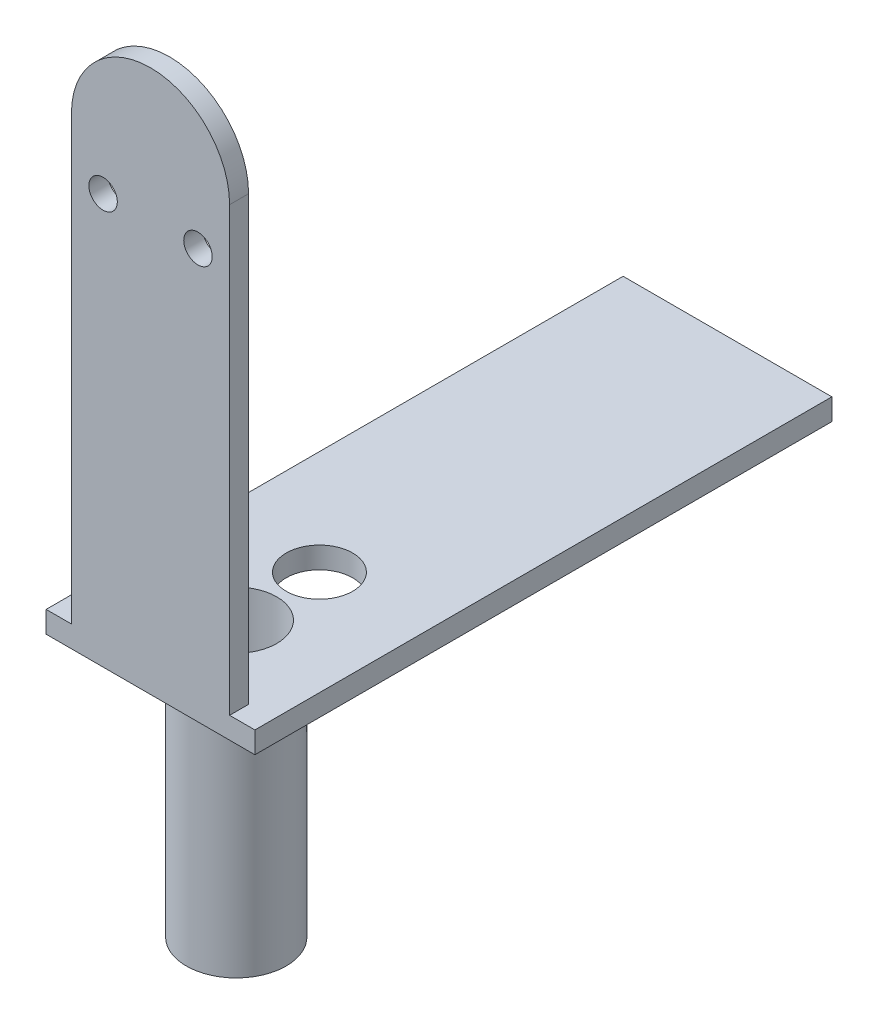
SolidWorks part; units mm, degrees
ref_plane "Front Plane" through (0, 0, 0) normal (0, 0, 1) x (1, 0, 0)
ref_plane "Top Plane" through (0, 0, 0) normal (0, 1, 0) x (1, 0, 0)
ref_plane "Right Plane" through (0, 0, 0) normal (1, 0, 0) x (0, 0, -1)
sketch "Sketch1" plane through (0, 0, 0) normal (0, 0, 1) x (1, 0, 0)
  line L0 (0, 0) -> (33, 0)
  line L1 (16.5, 0) -> (29, 0)
  line L2 (16.5, 0) -> (16.5, 9.4766)
  line L3 (4, 0) -> (4, 80.5)
  line L4 (29, 0) -> (29, 80.5)
  line L5 (0, 0) -> (0, 80.5)
  line L6 (0, 80.5) -> (4, 80.5)
  line L7 (33, 0) -> (33, 80.5)
  line L8 (33, 80.5) -> (29, 80.5)
  arc A0 (33, 80.5) -> (0, 80.5) centre (16.5, 80.5) ccw
  arc A1 (4, 80.5) -> (29, 80.5) centre (16.5, 80.5) cw
  point P5 (4, 0)
  dimension "D1" = 33
  dimension "D2" = 12.5
  dimension "D3" = 80.5
extrude "Boss-Extrude1" add sketch "Sketch1" along normal blind 71 contours L6 L5 L0 L3 | L6 A1 L8 A0 | L7 L8 L4 L0 region at (2, 40.25, 0) region at (16.5, 96.631, 0) region at (31, 40.25, 0)
sketch "Sketch2" plane through (0, 0, 71) normal (0, 0, 1) x (1, 0, 0)
  line L2 (33, 48.5) -> (0, 48.5)
  line L3 (0, 0) -> (0, 80.5) construction
  line L4 (0, 48.5) -> (0, 80.5)
  line L5 (33, 0) -> (33, 80.5) construction
  line L6 (33, 48.5) -> (33, 80.5)
  arc A0 (33, 80.5) -> (0, 80.5) centre (16.5, 80.5) ccw construction
  arc A1 (33, 80.5) -> (0, 80.5) centre (16.5, 80.5) ccw
  point P8 (16.5, 48.5)
extrude "Boss-Extrude2" add sketch "Sketch2" against normal blind 4
sketch "Sketch3" plane through (0, 0, 67) normal (0, 0, -1) x (-1, 0, 0)
  line L0 (-4, 48.5) -> (-29, 48.5) construction
  line L1 (-4, 48.5) -> (-29, 48.5)
  line L3 (-29, 44.5) -> (-4, 44.5)
  line L5 (0, 0) -> (0, 80.5) construction
  line L6 (0, 0) -> (0, 48.5)
  line L7 (-4, 48.5) -> (0, 48.5)
  line L8 (0, 0) -> (-3.8379, 0)
  line L9 (-4, 44.5) -> (-3.8379, 0)
  line L10 (-16.5, 44.5) -> (-16.5, 41.0104)
  line L11 (-33, 0) -> (-33, 48.5)
  line L12 (-29, 48.5) -> (-33, 48.5)
  line L13 (-29, 44.5) -> (-29.1621, 0)
  line L14 (-33, 0) -> (-29.1621, 0)
  line M8 (-29, 48.5) -> (-4, 48.5)
extrude "Boss-Extrude3" add sketch "Sketch3" against normal blind 34.2 contours L11 L14 L13 L3 L9 L8 L6 L7 L12 M8 region at (2, 47.9134, 67)
sketch "Sketch4" plane through (0, 0, 0) normal (0, 0, -1) x (-1, 0, 0)
  line L6 (-4, 80.5) -> (-4, 0)
  line L7 (-4, 0) -> (0, 0)
  line L8 (0, 0) -> (0, 80.5)
  line L9 (-33, 80.5) -> (-33, 0)
  line L10 (-33, 0) -> (-29, 0)
  line L11 (-29, 0) -> (-29, 80.5)
  line L12 (-4, 80.5) -> (-4, 0)
  line L13 (-4, 0) -> (0, 0)
  line L14 (0, 0) -> (0, 80.5)
  line L15 (-33, 80.5) -> (-33, 0)
  line L16 (-33, 0) -> (-29, 0)
  line L17 (-29, 0) -> (-29, 80.5)
  arc A2 (0, 80.5) -> (-33, 80.5) centre (-16.5, 80.5) ccw
  arc A3 (-4, 80.5) -> (-29, 80.5) centre (-16.5, 80.5) ccw
  arc A4 (0, 80.5) -> (-33, 80.5) centre (-16.5, 80.5) ccw
  arc A5 (-4, 80.5) -> (-29, 80.5) centre (-16.5, 80.5) ccw
  dimension "D1" = 0
extrude "Cut-Extrude1" cut sketch "Sketch4" against normal blind 13
sketch "Sketch5" plane through (0, 0, 71) normal (0, 0, 1) x (1, 0, 0)
  line L0 (0, 80.5) -> (33, 80.5)
  circle A0 centre (16.5, 80.5) radius 10
  dimension "D1" = 20
extrude "Cut-Extrude2" cut sketch "Sketch5" against normal blind 13 contours L0 A0 | L0 A0 region at (16.5, 84.7441, 71) region at (16.5, 76.2559, 71)
sketch "Sketch6" plane through (0, 0, 71) normal (0, 0, 1) x (1, 0, 0)
  line L0 (16.5, 70.5) -> (16.5, 73.1374)
  line L1 (16.5, 70.5) -> (33, 70.5)
  line L2 (33, 48.5) -> (33, 80.5) construction
  circle A0 centre (26.5, 70.5) radius 1.7
  circle A1 centre (6.5, 70.5) radius 1.7
  dimension "D2" = 3.4
  dimension "D1" = 6.5
extrude "Cut-Extrude3" cut sketch "Sketch6" against normal blind 13 contours A1 | L1 A0 | L1 A0 region at (26.5, 71.2215, 71) region at (26.5, 69.7785, 71) region at (6.5, 70.5, 71)
sketch "Sketch7" plane through (0, 0, 71) normal (0, 0, 1) x (1, 0, 0)
  circle A0 centre (6.5, 70.5) radius 3.25
  circle A1 centre (26.5, 70.5) radius 3.25
  dimension "D1" = 6.5
extrude "Cut-Extrude4" cut sketch "Sketch7" against normal blind 2.5
sketch "Sketch9" plane through (0, 0, 0) normal (0, -1, 0) x (1, 0, 0)
  line L0 (29.1621, 101.2) -> (29.1621, 71) construction
  line L1 (29.1621, 101.2) -> (29.1621, 71)
  line L2 (29.1621, 71) -> (29, 71)
  line L3 (29, 71) -> (29, 120)
  line L4 (29, 120) -> (29.1621, 101.2)
  line L6 (29, 67) -> (4, 67) construction
  line L7 (29, 67) -> (4, 67)
  line L8 (16.5, 67) -> (16.5, 71)
  line L9 (4, 120) -> (3.8379, 101.2)
  line L10 (4, 71) -> (4, 120)
  line L11 (3.8379, 71) -> (4, 71)
  line L12 (3.8379, 101.2) -> (3.8379, 71)
extrude "Boss-Extrude4" add sketch "Sketch9" against normal up to surface (44.5 mm away) contours L4 L1 L2 L3 | L9 L12 L11 L10 up to face at (16.5, 44.5, 79.7333)
sketch "Sketch10" plane through (0, 0, 101.2) normal (0, 0, 1) x (1, 0, 0)
  line L1 (40.2439, -6.5645) -> (-5.7585, -6.5645)
  line L2 (40.2439, -6.5645) -> (40.2439, 55.1467)
  line L3 (40.2439, 55.1467) -> (-5.7585, 55.1467)
  line L4 (-5.7585, -6.5645) -> (-5.7585, 55.1467)
  line L5 (40.2439, -6.5645) -> (-5.7585, 55.1467) construction
  line L6 (40.2439, 55.1467) -> (-5.7585, -6.5645) construction
  point P0 (17.2427, 24.2911)
extrude "Cut-Extrude5" cut sketch "Sketch10" along normal blind 42
fillet "Fillet1" radius 18 2 edges at (16.5, 44.5, 67) (16.5, 48.5, 71)
sketch "Sketch11" plane through (0, 0, 101.2) normal (0, 0, 1) x (1, 0, 0)
  line L0 (29, 0) -> (4, 0)
  line L8 (4, 44.5) -> (29, 44.5)
  line L9 (29, 44.5) -> (29, 0)
  line L10 (29, 0) -> (33, 0)
  line L11 (33, 0) -> (33, 48.5)
  line L12 (33, 48.5) -> (0, 48.5)
  line L13 (0, 48.5) -> (0, 0)
  line L14 (0, 0) -> (4, 0)
  line L15 (4, 0) -> (4, 44.5)
  line L18 (29, 0) -> (33, 0)
  line L19 (33, 0) -> (33, 48.5)
  line L20 (33, 48.5) -> (0, 48.5)
  line L21 (0, 48.5) -> (0, 0)
  line L22 (0, 0) -> (4, 0)
  dimension "D1" = 0
extrude "Boss-Extrude5" add sketch "Sketch11" along normal blind 4
fillet "Fillet3" radius 16.2 1 edges at (16.5, 48.5, 105.2)
fillet "Fillet4" radius 14 1 edges at (16.5, 44.5, 101.2)
sketch "Sketch12" plane through (0, 0, 0) normal (0, -1, 0) x (1, 0, 0)
  line L8 (4, 13) -> (4, 101.2)
  line L9 (4, 101.2) -> (29, 101.2)
  line L10 (29, 101.2) -> (29, 13)
  line L11 (29, 13) -> (33, 13)
  line L12 (33, 13) -> (33, 105.2)
  line L13 (33, 105.2) -> (0, 105.2)
  line L14 (0, 105.2) -> (0, 13)
  line L15 (0, 13) -> (4, 13)
  line L16 (4, 13) -> (4, 101.2)
  line L17 (4, 101.2) -> (29, 101.2)
  line L18 (29, 101.2) -> (29, 13)
  line L19 (29, 13) -> (33, 13)
  line L20 (33, 13) -> (33, 105.2)
  line L21 (33, 105.2) -> (0, 105.2)
  line L22 (0, 105.2) -> (0, 13)
  line L23 (0, 13) -> (4, 13)
  dimension "D1" = 0
extrude "Cut-Extrude6" cut sketch "Sketch12" against normal blind 10.6
sketch "Sketch13" plane through (0, 0, 13) normal (0, 0, -1) x (-1, 0, 0)
  line L6 (-33, 80.5) -> (-33, 10.6)
  line L7 (-33, 10.6) -> (-29, 10.6)
  line L8 (-29, 10.6) -> (-29, 80.5)
  line L9 (-4, 80.5) -> (-4, 10.6)
  line L10 (-4, 10.6) -> (0, 10.6)
  line L11 (0, 10.6) -> (0, 80.5)
  line L12 (-33, 80.5) -> (-33, 10.6)
  line L13 (-33, 10.6) -> (-29, 10.6)
  line L14 (-29, 10.6) -> (-29, 80.5)
  line L15 (-4, 80.5) -> (-4, 10.6)
  line L16 (-4, 10.6) -> (0, 10.6)
  line L17 (0, 10.6) -> (0, 80.5)
  arc A2 (-4, 80.5) -> (-29, 80.5) centre (-16.5, 80.5) ccw
  arc A3 (0, 80.5) -> (-33, 80.5) centre (-16.5, 80.5) ccw
  arc A4 (-4, 80.5) -> (-29, 80.5) centre (-16.5, 80.5) ccw
  arc A5 (0, 80.5) -> (-33, 80.5) centre (-16.5, 80.5) ccw
  dimension "D1" = 0
extrude "Boss-Extrude6" add sketch "Sketch13" along normal blind 4
ref_plane "Plane1" through (0, 0, 13) normal (0, 0, -1) x (-1, 0, 0)
sketch "Sketch14" plane through (0, 0, 13) normal (0, 0, -1) x (-1, 0, 0)
  line L0 (-29, 10.6) -> (-4, 10.6)
  line L6 (-33, 80.5) -> (-33, 10.6)
  line L7 (-33, 10.6) -> (-29, 10.6)
  line L8 (-29, 10.6) -> (-29, 80.5)
  line L9 (-4, 80.5) -> (-4, 10.6)
  line L10 (-4, 10.6) -> (0, 10.6)
  line L11 (0, 10.6) -> (0, 80.5)
  line L12 (-33, 80.5) -> (-33, 10.6)
  line L13 (-33, 10.6) -> (-29, 10.6)
  line L16 (-4, 10.6) -> (0, 10.6)
  line L17 (0, 10.6) -> (0, 80.5)
  arc A2 (0, 80.5) -> (-33, 80.5) centre (-16.5, 80.5) ccw
  arc A3 (-4, 80.5) -> (-29, 80.5) centre (-16.5, 80.5) ccw
  arc A4 (0, 80.5) -> (-33, 80.5) centre (-16.5, 80.5) ccw
  dimension "D1" = 0
extrude "Cut-Extrude7" cut sketch "Sketch14" against normal blind 148
sketch "Sketch15" plane through (0, 0, 13) normal (0, 0, 1) x (1, 0, 0)
  line L0 (4, 10.6) -> (29, 10.6)
  line L6 (29, 80.5) -> (29, 10.6)
  line L7 (29, 10.6) -> (33, 10.6)
  line L8 (33, 10.6) -> (33, 80.5)
  line L9 (0, 80.5) -> (0, 10.6)
  line L10 (0, 10.6) -> (4, 10.6)
  line L11 (4, 10.6) -> (4, 80.5)
  line L12 (29, 80.5) -> (29, 10.6)
  line L13 (29, 10.6) -> (33, 10.6)
  line L17 (4, 10.6) -> (4, 80.5)
  arc A2 (33, 80.5) -> (0, 80.5) centre (16.5, 80.5) ccw
  arc A3 (29, 80.5) -> (4, 80.5) centre (16.5, 80.5) ccw
  arc A5 (29, 80.5) -> (4, 80.5) centre (16.5, 80.5) ccw
  line M10 (29, 80.5) -> (29, 10.6)
  line M16 (4, 10.6) -> (4, 80.5)
  arc M17 (4, 80.5) -> (29, 80.5) centre (16.5, 80.5) cw
  dimension "D1" = 0
extrude "Boss-Extrude7" add sketch "Sketch15" along normal blind 3 separate body contours L0 M16 M10 M17 region at (16.5, 50.5076, 13)
sketch "Sketch16" plane through (0, 0, 9) normal (0, 0, -1) x (-1, 0, 0)
  line L6 (-33, 80.5) -> (-33, 10.6)
  line L7 (-33, 10.6) -> (-29, 10.6)
  line L8 (-29, 10.6) -> (-29, 80.5)
  line L9 (-4, 80.5) -> (-4, 10.6)
  line L10 (-4, 10.6) -> (0, 10.6)
  line L11 (0, 10.6) -> (0, 80.5)
  line L12 (-33, 80.5) -> (-33, 10.6)
  line L13 (-33, 10.6) -> (-29, 10.6)
  line L14 (-29, 10.6) -> (-29, 80.5)
  line L15 (-4, 80.5) -> (-4, 10.6)
  line L16 (-4, 10.6) -> (0, 10.6)
  line L17 (0, 10.6) -> (0, 80.5)
  arc A2 (0, 80.5) -> (-33, 80.5) centre (-16.5, 80.5) ccw
  arc A3 (-4, 80.5) -> (-29, 80.5) centre (-16.5, 80.5) ccw
  arc A4 (0, 80.5) -> (-33, 80.5) centre (-16.5, 80.5) ccw
  arc A5 (-4, 80.5) -> (-29, 80.5) centre (-16.5, 80.5) ccw
  dimension "D1" = 0
extrude "Cut-Extrude8" cut sketch "Sketch16" against normal blind 14
sketch "Sketch17" plane through (0, 0, 13) normal (0, 0, -1) x (-1, 0, 0)
  line L0 (-16.5, 93) -> (-16.5, 68)
  line L1 (-16.5, 68) -> (-4, 68)
  line L2 (-4, 10.6) -> (-4, 80.5) construction
  arc A0 (-4, 80.5) -> (-29, 80.5) centre (-16.5, 80.5) ccw construction
  circle A1 centre (-9, 72) radius 2.25
  circle A2 centre (-24, 72) radius 2.25
  dimension "D2" = 4.5
  dimension "D3" = 5
  dimension "D4" = 4
  dimension "D1" = 25
extrude "Cut-Extrude9" cut sketch "Sketch17" against normal blind 14 contours A2 | A1 region at (24, 72, 13)
sketch "Sketch18" plane through (0, 10.6, 0) normal (0, -1, 0) x (1, 0, 0)
  line L0 (29, 16) -> (29, -76.2)
  line L1 (29, 16) -> (4, 16)
  line L2 (4, 16) -> (4, -76.2)
  line L3 (4, -76.2) -> (29, -76.2)
  dimension "D1" = 92.2
extrude "Boss-Extrude8" add sketch "Sketch18" along normal blind 4
sketch "Sketch19" plane through (0, 6.6, 0) normal (0, -1, 0) x (1, 0, 0)
  line L0 (4, 16) -> (0, 16)
  line L1 (0, 16) -> (0, -76.2)
  line L2 (4, -76.2) -> (0, -76.2)
  line L3 (4, -76.2) -> (4, 16)
  line L4 (16.5, 16) -> (16.5, 9.1971)
  line L5 (29, 16) -> (4, 16) construction
  line L6 (29, -76.2) -> (33, -76.2)
  line L7 (33, 16) -> (33, -76.2)
  line L8 (29, 16) -> (33, 16)
  line L9 (29, -76.2) -> (29, 16)
  line M7 (4, 16) -> (4, -76.2)
  line M9 (29, -76.2) -> (29, 16)
extrude "Boss-Extrude9" add sketch "Sketch19" against normal up to surface (4 mm away) contours L2 L0 L1 M7 | L8 L6 L7 M9 region at (2, 6.6, -30.1) region at (31, 6.6, -30.1) up to face at (16.5, 10.6, -31.6)
sketch "Sketch20" plane through (0, 6.6, 0) normal (0, -1, 0) x (1, 0, 0)
  line L0 (16.5, 16) -> (16.5, -10.7)
  line L1 (33, 16) -> (0, 16) construction
  circle A0 centre (16.5, -10.7) radius 5.25
  dimension "D2" = 10.5
  dimension "D1" = 26.7
extrude "Cut-Extrude10" cut sketch "Sketch20" against normal up to surface (4 mm away) contours A0 region at (12.8927, 6.6, -14.3073) up to face at (16.5, 10.6, -7.8)
sketch "Sketch21" plane through (0, 6.6, 0) normal (0, -1, 0) x (1, 0, 0)
  line L4 (33, 16) -> (0, 16)
  line L5 (0, 16) -> (0, -76.2)
  line L6 (0, -76.2) -> (33, -76.2)
  line L7 (33, -76.2) -> (33, 16)
  line L8 (33, 16) -> (0, 16)
  line L9 (0, 16) -> (0, -76.2)
  line L10 (0, -76.2) -> (33, -76.2)
  line L11 (33, -76.2) -> (33, 16)
  dimension "D1" = 0
extrude "Cut-Extrude11" cut sketch "Sketch21" against normal blind 0.6
sketch "Sketch22" plane through (0, 7.2, 0) normal (0, -1, 0) x (1, 0, 0)
  line L0 (16.5, 16) -> (16.5, 1.3)
  line L1 (33, 16) -> (0, 16) construction
  circle A0 centre (16.5, 1.3) radius 5.25
  dimension "D2" = 10.5
  dimension "D1" = 14.7
extrude "Cut-Extrude12" cut sketch "Sketch22" against normal up to surface (3.4 mm away) contours A0 region at (12.8927, 7.2, -2.3073) up to face at (16.5, 10.6, -15.95)
sketch "Sketch23" plane through (0, 7.2, 0) normal (0, -1, 0) x (1, 0, 0)
  line L0 (16.5, -5.45) -> (16.5, 10.35)
  circle A0 centre (16.5, -10.7) radius 5.25 construction
  circle A1 centre (16.5, 2.45) radius 7.9
  circle A2 centre (16.5, 2.45) radius 6.4
  dimension "D1" = 15.8
extrude "Boss-Extrude10" add sketch "Sketch23" along normal blind 40 contours A2 L0 A1 | A2 L0 A1 region at (8.7766, 7.2, 2.45) region at (16.6766, 7.2, -4.7)
sketch "Sketch24" plane through (0, 7.2, 0) normal (0, -1, 0) x (1, 0, 0)
  circle A2 centre (16.5, 2.45) radius 6.4 construction
  circle A3 centre (16.5, 2.45) radius 6.4
extrude "Cut-Extrude13" cut sketch "Sketch24" against normal up to surface (3.4 mm away) up to face at (16.5, 10.6, -3.95)
sketch "Sketch25" plane through (0, 10.6, 0) normal (0, 1, 0) x (1, 0, 0)
  line L0 (16.5, 76.2) -> (16.5, 74.7)
  line L1 (0, 76.2) -> (33, 76.2) construction
  line L2 (16.5, 74.7) -> (6.5, 74.7)
  line L3 (6.5, 74.7) -> (6.5, 72.7)
  line L4 (16.5, 74.7) -> (26.5, 74.7)
  line L5 (26.5, 74.7) -> (26.5, 72.7)
  line L6 (26.5, 72.7) -> (6.5, 72.7)
extrude "Boss-Extrude11" add sketch "Sketch25" along normal blind 15 contours L6 L5 L4 L2 L3 region at (16.5, 10.6, -73.7)
sketch "Sketch26" plane through (0, 10.6, 0) normal (0, 1, 0) x (1, 0, 0)
  line L0 (21.5, 74.7) -> (11.5, 74.7)
  line L1 (6.5, 74.7) -> (26.5, 74.7) construction
  line L2 (11.5, 74.7) -> (16.5, 74.7)
  line L3 (11.5, 74.7) -> (11.5, 76.2)
  line L4 (0, 76.2) -> (33, 76.2) construction
  line L5 (11.5, 76.2) -> (21.5, 76.2)
  line L6 (21.5, 76.2) -> (21.5, 74.7)
  point P5 (16.5, 74.7)
  dimension "D1" = 10
extrude "Boss-Extrude12" add sketch "Sketch26" along normal up to surface (15 mm away) contours L3 L5 L6 L0 up to face at (16.5, 25.6, -73.7)
sketch "Sketch27" plane through (0, 10.6, 0) normal (0, 1, 0) x (1, 0, 0)
  line L8 (6.5, 72.7) -> (26.5, 72.7)
  line L9 (26.5, 72.7) -> (26.5, 74.7)
  line L10 (26.5, 74.7) -> (21.5, 74.7)
  line L11 (21.5, 74.7) -> (21.5, 76.2)
  line L12 (21.5, 76.2) -> (11.5, 76.2)
  line L13 (11.5, 76.2) -> (11.5, 74.7)
  line L14 (11.5, 74.7) -> (6.5, 74.7)
  line L15 (6.5, 74.7) -> (6.5, 72.7)
  line L16 (6.5, 72.7) -> (26.5, 72.7)
  line L17 (26.5, 72.7) -> (26.5, 74.7)
  line L18 (26.5, 74.7) -> (21.5, 74.7)
  line L19 (21.5, 74.7) -> (21.5, 76.2)
  line L20 (21.5, 76.2) -> (11.5, 76.2)
  line L21 (11.5, 76.2) -> (11.5, 74.7)
  line L22 (11.5, 74.7) -> (6.5, 74.7)
  line L23 (6.5, 74.7) -> (6.5, 72.7)
  dimension "D1" = 0
extrude "Cut-Extrude14" cut sketch "Sketch27" along normal up to surface (15 mm away) up to face at (16.5, 25.6, -74.575)
sketch "Sketch28" plane through (0, 0, -76.2) normal (0, 0, -1) x (-1, 0, 0)
  line L4 (0, 10.6) -> (-33, 10.6)
  line L5 (-33, 10.6) -> (-33, 7.2)
  line L6 (-33, 7.2) -> (0, 7.2)
  line L7 (0, 7.2) -> (0, 10.6)
  line L8 (0, 10.6) -> (-33, 10.6)
  line L9 (-33, 10.6) -> (-33, 7.2)
  line L10 (-33, 7.2) -> (0, 7.2)
  line L11 (0, 7.2) -> (0, 10.6)
  dimension "D1" = 0
extrude "Cut-Extrude15" cut sketch "Sketch28" against normal blind 1
